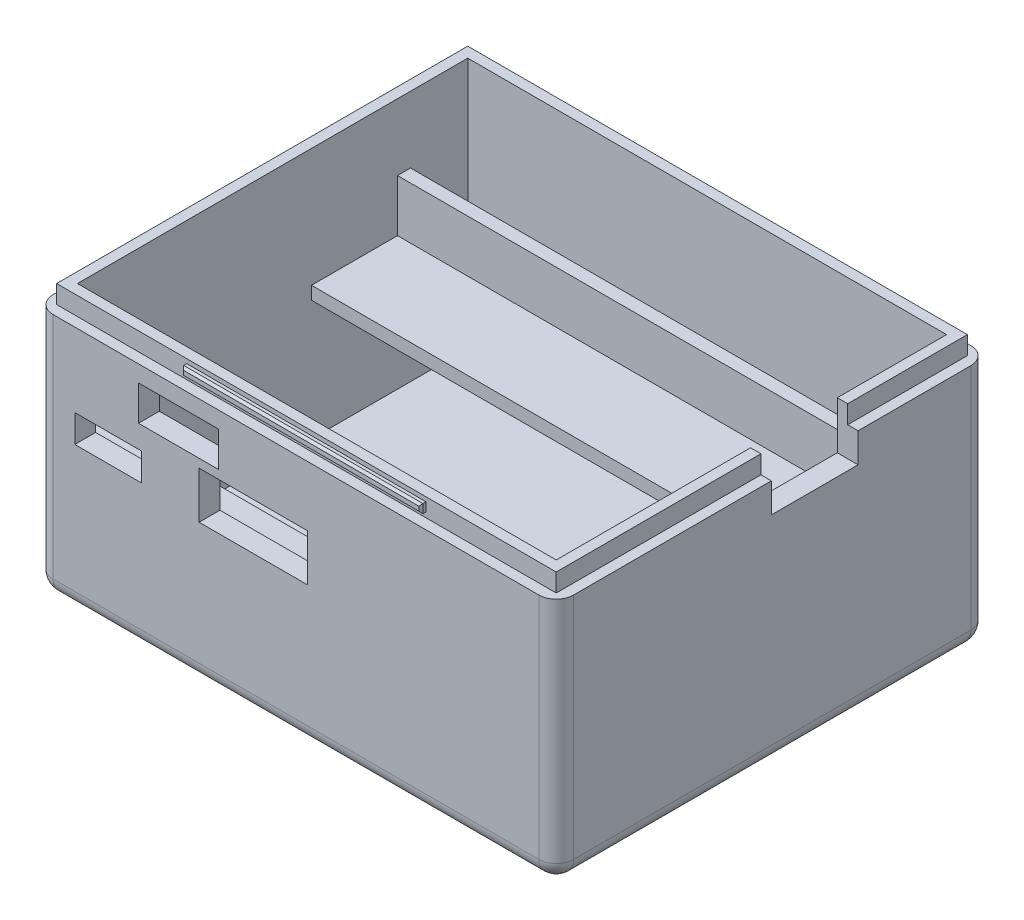
SolidWorks part; units mm, degrees
ref_plane "Front Plane" through (0, 0, 0) normal (0, 0, 1) x (1, 0, 0)
ref_plane "Top Plane" through (0, 0, 0) normal (0, 1, 0) x (1, 0, 0)
ref_plane "Right Plane" through (0, 0, 0) normal (1, 0, 0) x (0, 0, -1)
sketch "BatteryAndOuterWalls" plane through (0, 0, 0) normal (0, 1, 0) x (1, 0, 0)
  line L0 (30, -24.9) -> (30, 24.9)
  line L1 (27.6, -22.5) -> (-27.6, -22.5)
  line L2 (27.6, -22.5) -> (27.6, 22.5)
  line L3 (27.6, 22.5) -> (-27.6, 22.5)
  line L4 (-27.6, -22.5) -> (-27.6, 22.5)
  line L5 (27.6, -22.5) -> (-27.6, 22.5) construction
  line L6 (27.6, 22.5) -> (-27.6, -22.5) construction
  line L7 (30, 24.9) -> (-30, 24.9)
  line L8 (-30, -24.9) -> (-30, 24.9)
  line L9 (30, -24.9) -> (-30, -24.9)
  point P0 (0, 0)
  dimension "D1" = 55.2
  dimension "D2" = 45
  dimension "D4" = 60
  dimension "D5" = 49.8
  dimension "D3" = 2.4
extrude "Walls" add sketch "BatteryAndOuterWalls" along normal blind 29
sketch "SinkRim" plane through (0, 29, 0) normal (0, 1, 0) x (1, 0, 0)
  line L0 (-28.8, 23.7) -> (-28.8, -23.7)
  line L5 (-27.6, 22.5) -> (27.6, 22.5)
  line L6 (-27.6, 22.5) -> (-27.6, -22.5)
  line L7 (-27.6, -22.5) -> (27.6, -22.5)
  line L8 (27.6, 22.5) -> (27.6, -22.5)
  line L9 (-28.8, -23.7) -> (28.8, -23.7)
  line L10 (28.8, 23.7) -> (28.8, -23.7)
  line L11 (-28.8, 23.7) -> (28.8, 23.7)
  line L12 (-30, 24.9) -> (30, 24.9)
  line L13 (30, 24.9) -> (30, -24.9)
  line L14 (-30, -24.9) -> (30, -24.9)
  line L15 (-30, 24.9) -> (-30, -24.9)
  line M5 (-30, -24.9) -> (30, -24.9)
  line M6 (30, -24.9) -> (30, 24.9)
  line M7 (30, 24.9) -> (-30, 24.9)
  line M8 (-30, 24.9) -> (-30, -24.9)
  dimension "D1" = 1.2
  dimension "D2" = 1.2
sketch "Sketch2" plane through (0, 0, 0) normal (0, -1, 0) x (1, 0, 0)
  line L0 (-30, 24.9) -> (30, 24.9) construction
  line L5 (-30, 24.9) -> (30, 24.9)
  line L6 (-30, 24.9) -> (-30, -24.9)
  line L7 (-30, -24.9) -> (30, -24.9)
  line L8 (30, 24.9) -> (30, -24.9)
  line L9 (-30, -24.9) -> (-30, 24.9) construction
extrude "Bottom" add sketch "Sketch2" along normal blind 1.5
extrude "Top-Cut" cut sketch "SinkRim" against normal blind 2.1 contours L0 L11 L10 L9 M8 M5 M6 M7 region at (0, 29, -24.1203)
sketch "FrontRail" plane through (30, 0, 0) normal (1, 0, 0) x (0, 0, -1)
  line L0 (13.6255, 19.3303) -> (-12.2825, 19.3303) construction
  line L1 (-22.5132, 29) -> (22.5, 29)
  line L3 (-22.5132, 0) -> (22.5, 0)
  line L4 (22.5, 29) -> (22.5, 0)
  line L5 (24.9, -1.5) -> (-24.9, -1.5) construction
  line L6 (24.9, 26.9) -> (24.9, -1.5) construction
  line L7 (23.7, 29) -> (-23.7, 29) construction
  line L8 (-22.5132, 0) -> (-22.5132, 29)
  line L31 (-22.5132, 12.5) -> (-19.5132, 12.5)
  line L36 (-22.5132, 12.5) -> (-22.5132, 14)
  line L37 (-22.5132, 14) -> (-19.5132, 14)
  line L38 (-19.5132, 12.5) -> (-19.5132, 14)
  line L39 (-4.5132, 15.3303) -> (22.5, 15.3303)
  line L40 (-4.5132, 15.3303) -> (-4.5132, 13.8303)
  line L41 (-4.5132, 13.8303) -> (22.5, 13.8303)
  line L42 (22.5, 15.3303) -> (22.5, 13.8303)
  line L44 (14.4, 15.3303) -> (15.9, 15.3303)
  line L45 (14.4, 15.3303) -> (14.4, 21.3303)
  line L46 (14.4, 21.3303) -> (15.9, 21.3303)
  line L47 (15.9, 15.3303) -> (15.9, 21.3303)
  dimension "D10" = 0
  dimension "D6" = 3
  dimension "D1" = 12.5
  dimension "D2" = 1.5
  dimension "D3" = 2.4
  dimension "D4" = 0
  dimension "D5" = 1.5
  dimension "D7" = 1.5
  dimension "D8" = 4
  dimension "D9" = 15
  dimension "D11" = 6
  dimension "D12" = 0
  dimension "D13" = 1.5
  dimension "D14" = 8.1
  dimension "D15" = 6.6
extrude "PCB-Supports" add sketch "FrontRail" against normal blind 60 contours L41 L42 L39 L40 | L37 L38 L31 L36 | L45 L44 L47 L46
sketch "Sketch3" plane through (0, 0, 0) normal (0, 1, 0) x (1, 0, 0)
  line L1 (-27.6, 22.5) -> (27.6, 22.5)
  line L2 (-27.6, 22.5) -> (-27.6, -22.5)
  line L3 (-27.6, -22.5) -> (27.6, -22.5)
  line L4 (27.6, 22.5) -> (27.6, -22.5)
  line L5 (27.6, 22.5) -> (-27.6, 22.5)
  line L6 (27.6, 22.5) -> (27.6, 15.9)
  line L7 (27.6, 15.9) -> (-27.6, 15.9)
  line L8 (-27.6, 22.5) -> (-27.6, 15.9)
  line L9 (-27.6, -4.5132) -> (27.6, -4.5132)
  line L10 (-27.6, -4.5132) -> (-27.6, 4.4868)
  line L11 (-27.6, 4.4868) -> (27.6, 4.4868)
  line L12 (27.6, -4.5132) -> (27.6, 4.4868)
  dimension "D1" = 9
  dimension "D2" = 6.6
extrude "Battery-Insertion-Cut" cut sketch "Sketch3" along normal blind 25 contours L7 L4 L1 L2 | L11 L12 L9 L10 region at (0, 0, -19.2)
sketch "USB_FRONT" plane through (0, 0, 24.9) normal (0, 0, 1) x (1, 0, 0)
  line L0 (-30, 26.9) -> (30, 26.9) construction
  line L1 (-25.5021, 15.1801) -> (-17.8193, 15.1801)
  line L2 (-25.5021, 15.1801) -> (-25.5021, 18.3701)
  line L3 (-25.5021, 18.3701) -> (-17.8193, 18.3701)
  line L4 (-17.8193, 15.1801) -> (-17.8193, 18.3701)
  line L5 (-11.1723, 14.5801) -> (-11.1723, 19.9801)
  line L10 (-11.1723, 19.9801) -> (1.3277, 19.9801)
  line L11 (1.3277, 14.5801) -> (1.3277, 19.9801)
  line L12 (-11.1723, 14.5801) -> (1.3277, 14.5801)
  line L14 (-18.1623, 20.9683) -> (-8.9623, 20.9683)
  line L15 (-18.1623, 20.9683) -> (-18.1623, 25)
  line L16 (-18.1623, 25) -> (-8.9623, 25)
  line L17 (-8.9623, 20.9683) -> (-8.9623, 25)
  dimension "D1" = 1.9
  dimension "D2" = 0.9882
  dimension "D3" = 2.5982
  dimension "D4" = 9.2
  dimension "D5" = 5.9317
extrude "USB-Front-Cut" cut sketch "USB_FRONT" against normal blind 10
sketch "USB-Right-Sketch" plane through (30, 0, 0) normal (1, 0, 0) x (0, 0, -1)
  line L0 (24.9, 26.9) -> (24.9, -1.5) construction
  line L1 (-0.1, 29) -> (9.9, 29)
  line L2 (-0.1, 29) -> (-0.1, 23.5)
  line L3 (-0.1, 23.5) -> (9.9, 23.5)
  line L4 (9.9, 29) -> (9.9, 23.5)
  line L5 (23.7, 29) -> (-23.7, 29) construction
  line L6 (-24.9, 26.9) -> (24.9, 26.9) construction
  dimension "D1" = 0
  dimension "D2" = 5.5
  dimension "D3" = 15
  dimension "D4" = 10
  dimension "D5" = 3.4
extrude "USB-Side" cut sketch "USB-Right-Sketch" against normal blind 5
ref_plane "Plane1" through (0, 0, 0) normal (0, 0, 1) x (1, 0, 0)
sketch "Sketch7" plane through (0, 0, 23.7) normal (0, 0, 1) x (1, 0, 0)
  line L0 (-28.8, 29) -> (28.8, 29) construction
  line L1 (-13.8, 28.5) -> (13.8, 28.5)
  line L2 (-13.8, 28.5) -> (-13.8, 27.5)
  line L3 (-13.8, 27.5) -> (13.8, 27.5)
  line L4 (13.8, 28.5) -> (13.8, 27.5)
  line L5 (-30, 26.9) -> (30, 26.9) construction
  line L6 (-28.8, 26.9) -> (-28.8, 29) construction
  line L7 (28.8, 26.9) -> (28.8, 29) construction
  dimension "D1" = 0.5
  dimension "D2" = 1
  dimension "D3" = 0.6
  dimension "D4" = 15
  dimension "D5" = 15
extrude "Lid-Ridge-Front" add sketch "Sketch7" along normal blind 0.6
chamfer "Lid-Ridge-Front-Chamfer" distance 0.25 angle 45 4 edges at (0, 28.5, 24.3) (13.8, 28, 24.3) (0, 27.5, 24.3) (-13.8, 28, 24.3)
mirror "Mirror1" about plane through (0, 0, 0) normal (0, 0, 1) of "Lid-Ridge-Front-Chamfer", "Lid-Ridge-Front"
fillet "Fillet1" radius 2 8 edges at (0, -1.5, 24.9) (30, 12.7, 24.9) (-30, 12.7, 24.9) (-30, -1.5, 0) (-30, 12.7, -24.9) (0, -1.5, -24.9) (30, -1.5, 0) (30, 12.7, -24.9)
